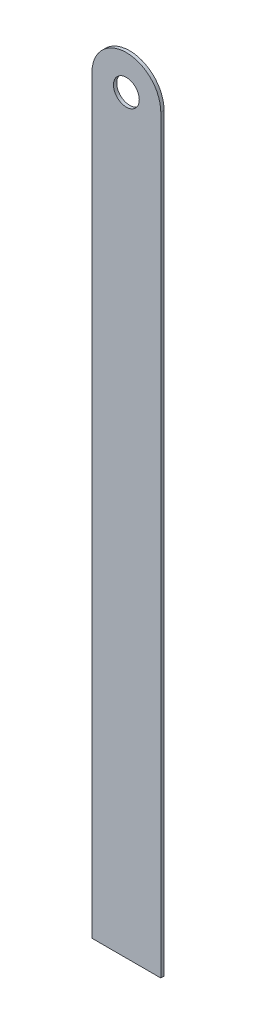
SolidWorks part; units mm, degrees
material "Alloy Steel"
ref_plane "Front" through (0, 0, 0) normal (0, 0, 1) x (1, 0, 0)
ref_plane "Top" through (0, 0, 0) normal (0, 1, 0) x (1, 0, 0)
ref_plane "Right" through (0, 0, 0) normal (1, 0, 0) x (0, 0, -1)
sketch "Sketch1" plane through (0, 0, 0) normal (0, 0, 1) x (1, 0, 0)
  line L1 (-12.7, 138.43) -> (12.7, 138.43)
  line L2 (-12.7, 138.43) -> (-12.7, -138.43)
  line L3 (-12.7, -138.43) -> (12.7, -138.43)
  line L4 (12.7, 138.43) -> (12.7, -138.43)
  line L5 (-12.7, 138.43) -> (12.7, -138.43) construction
  line L6 (-12.7, -138.43) -> (12.7, 138.43) construction
  arc A0 (-12.7, 138.43) -> (12.7, 138.43) centre (0, 138.43) cw
  point P0 (0, 0)
  dimension "D3" = 12.7
  dimension "D1" = 276.86
  dimension "D2" = 25.4
extrude "Boss-Extrude1" add sketch "Sketch1" along normal blind 1.2 contours L4 L1 L2 L3 | A0 L1 region at (0, 143.82, 0) region at (0, 0, 0)
sketch "Sketch2" plane through (0, 0, 1.2) normal (0, 0, 1) x (1, 0, 0)
  circle A0 centre (0, 138.43) radius 4.7625
  dimension "D1" = 9.525
extrude "Cut-Extrude1" cut sketch "Sketch2" against normal through all
